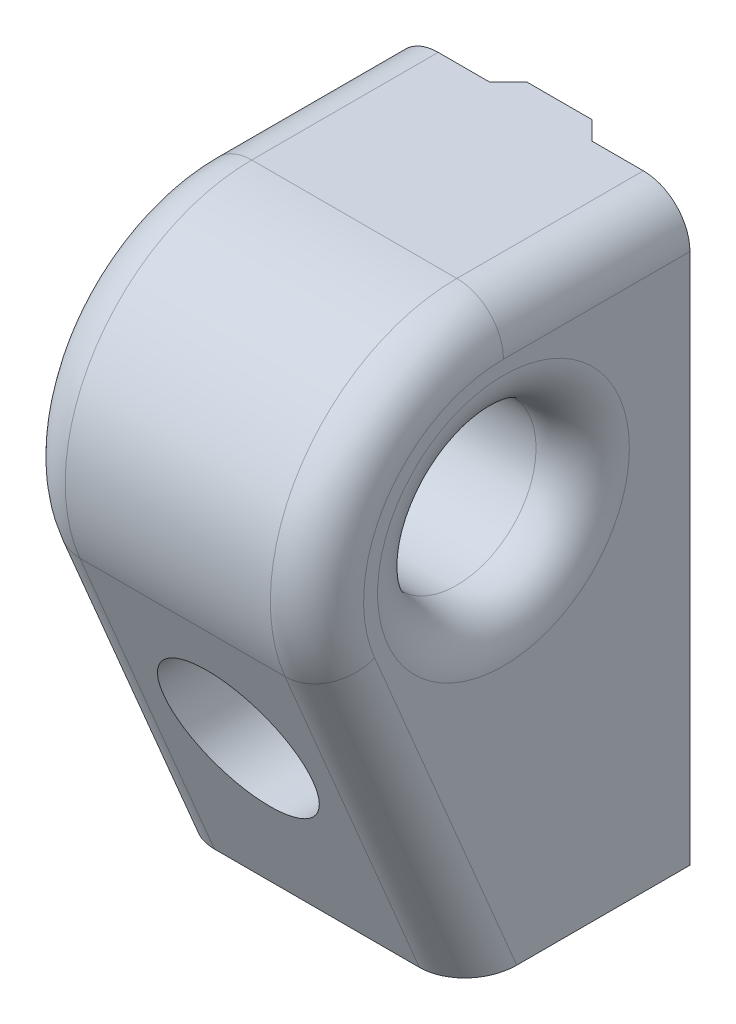
SolidWorks part; units mm, degrees
material "ABS"
ref_plane "Front" through (0, 0, 0) normal (0, 0, 1) x (1, 0, 0)
ref_plane "Top" through (0, 0, 0) normal (0, 1, 0) x (1, 0, 0)
ref_plane "Right" through (0, 0, 0) normal (1, 0, 0) x (0, 0, -1)
sketch "Esquisse1" plane through (0, 0, 0) normal (1, 0, 0) x (0, 0, -1)
  line L0 (0, 0) -> (0, 31)
  line L1 (0, 31) -> (-10, 31)
  line L2 (-19.2148, 17.1157) -> (-12, 0)
  line L3 (-12, 0) -> (0, 0)
  circle A0 centre (-10, 21) radius 4.25
  arc A1 (-10, 31) -> (-19.2148, 17.1157) centre (-10, 21) ccw
  dimension "D1" = 8.5
  dimension "D2" = 10
  dimension "D3" = 21
  dimension "D4" = 10
  dimension "D5" = 12
extrude "Boss.-Extru.1" add sketch "Esquisse1" along normal mid plane 16
sketch "Esquisse2" plane through (0, 0, 0) normal (0, 0, -1) x (-1, 0, 0)
  line L0 (-8, 31) -> (8, 31) construction
  line L1 (-2.75, 31) -> (2.75, 31)
  line L2 (-2.75, 31) -> (-2.75, 0)
  line L3 (-2.75, 0) -> (2.75, 0)
  line L4 (2.75, 31) -> (2.75, 0)
  dimension "D1" = 5.5
extrude "Boss.-Extru.2" add sketch "Esquisse2" along normal blind 1
chamfer "Chanfrein1" distance 1 angle 45 2 edges at (-2.75, 15.5, -1) (2.75, 15.5, -1)
sketch "Esquisse3" plane through (0, 0, -1) normal (0, 0, -1) x (-1, 0, 0)
  line L0 (2.75, 0) -> (8, 0) construction
  circle A0 centre (0, 10) radius 2.1
  dimension "D1" = 4.2
  dimension "D2" = 10
extrude "Enlèv. mat.-Extru.1" cut sketch "Esquisse3" against normal through all
sketch "Esquisse4" plane through (0, 0, 0) normal (0, 0, -1) x (-1, 0, 0)
  circle A0 centre (0, 10) radius 4
  arc A1 (1.75, 11.1608) -> (-1.75, 11.1608) centre (0, 10) ccw construction
  dimension "D1" = 8
extrude "Enlèv. mat.-Extru.2" cut sketch "Esquisse4" against normal through all from offset 5 offset against normal yes
fillet "Congé1" radius 2.5 8 edges at (-8, 31, 5) (-8, 26.5298, 18.332) (8, 31, 5) (8, 26.5298, 18.332) (-8, 21, 5.75) (8, 21, 5.75) (-8, 8.5578, 15.6074) (8, 8.5578, 15.6074)
sketch "Esquisse5" plane through (-8, 0, 0) normal (-1, 0, 0) x (0, 0, 1)
  circle A0 centre (10, 21) radius 6.75 construction
  circle A1 centre (10, 21) radius 6.75
extrude "Boss.-Extru.3" [suppressed] add sketch "Esquisse5" against normal blind 0.2
